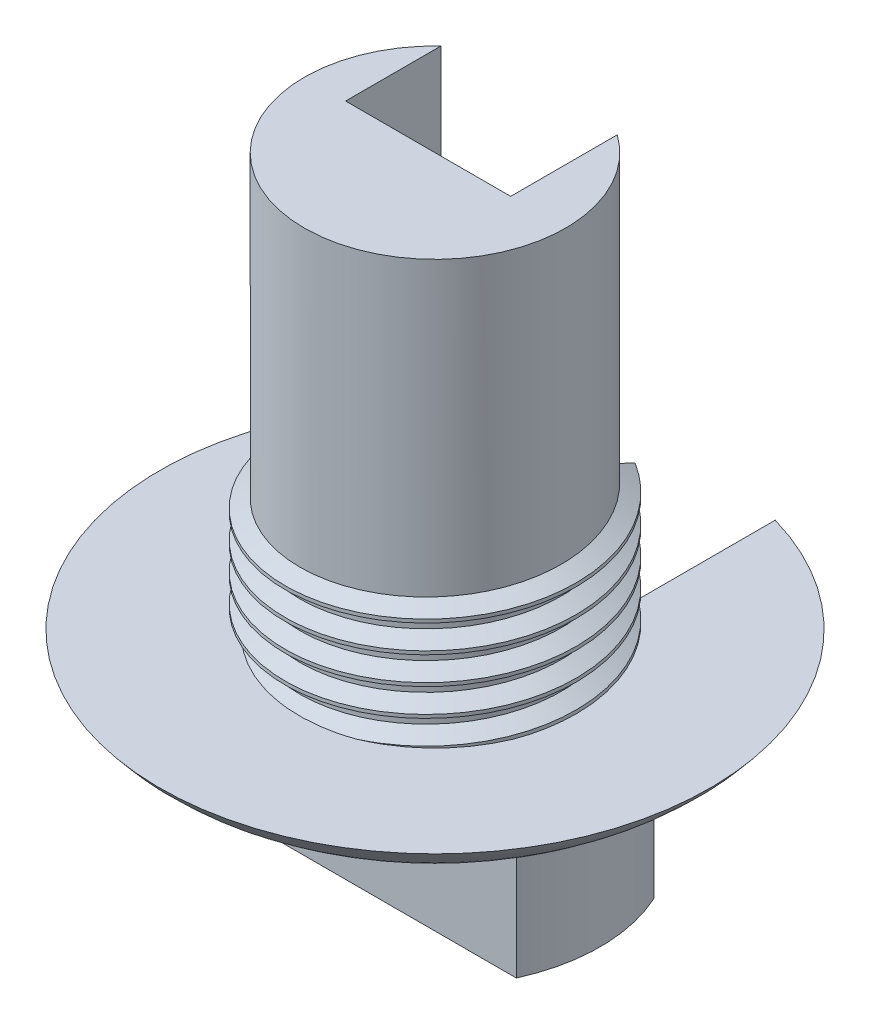
SolidWorks part; units mm, degrees
ref_plane "Alzado" through (0, 0, 0) normal (0, 0, 1) x (1, 0, 0)
ref_plane "Planta" through (0, 0, 0) normal (0, 1, 0) x (1, 0, 0)
ref_plane "Vista lateral" through (0, 0, 0) normal (1, 0, 0) x (0, 0, -1)
sketch "Croquis1" plane through (0, 0, 0) normal (0, 1, 0) x (1, 0, 0)
  circle A0 centre (0, 0) radius 20
  dimension "D1" = 40
extrude "Saliente-Extruir1" add sketch "Croquis1" along normal blind 4
sketch "Croquis2" plane through (0, 4, 0) normal (0, 1, 0) x (1, 0, 0)
  circle A0 centre (0, 0) radius 9.5
  dimension "D1" = 19
extrude "Saliente-Extruir2" add sketch "Croquis2" along normal blind 10
thread "Rosca1" pitch 2 method extrude profile "Perfil de rosca1" start angle 0, offset 0, length 12, pitch 2, diameter 19
ref_plane "Plano1" through (-9.5, 14, 0) normal (0, 0, 1) x (-1, 0, 0)
sketch "Perfil de rosca1" plane through (-9.5, 14, 0) normal (0, 0, 1) x (-1, 0, 0)
  line L0 (0, 0) -> (0, 2) construction
  line L1 (0, 0) -> (1.0825, 0.625)
  line L2 (1.0825, 0.625) -> (1.0825, 0.875)
  line L3 (1.0825, 0.875) -> (0, 1.5)
  line L4 (1.0825, 0.75) -> (0, 0.75) construction
  line L11 (0, 0) -> (0, 1.5)
  point P2 (0, 0)
  dimension "Pitch" = 2
  dimension "Profile_Angle" = 60
  dimension "Profile_Land" = 0.25
  dimension "Profile_Height" = 1.0825
fillet "Redondeo1" radius 10 1 edges at (0, 0, 20)
sketch "Croquis6" plane through (0, 0, 0) normal (0, 1, 0) x (1, 0, 0)
  line L1 (-10.9087, -5) -> (10.9087, -5)
  line L3 (-10.9087, 5) -> (10.9087, 5)
  circle A0 centre (0, 0) radius 12 construction
  arc A1 (10.9087, -5) -> (10.9087, 5) centre (0, 0) ccw
  arc A2 (-10.9087, 5) -> (-10.9087, -5) centre (0, 0) ccw
  dimension "D1" = 10
  dimension "D2" = 10
extrude "Saliente-Extruir3" add sketch "Croquis6" against normal blind 10 contours L3 A1 L1 A2
sketch "Croquis8" plane through (0, 14, 0) normal (0, 1, 0) x (1, 0, 0)
  circle A1 centre (0, 0) radius 9.5
  circle A2 centre (0, 0) radius 9.5
  dimension "D1" = 0
extrude "Saliente-Extruir4" add sketch "Croquis8" along normal blind 20
sketch "Croquis9" plane through (0, 0, 0) normal (0, 1, 0) x (1, 0, 0)
  line L0 (-6.5, 0) -> (5.5, 0)
  line L3 (-6.5, 0) -> (-6.5, 26.0113)
  line L4 (-6.5, 26.0113) -> (5.5, 26.0113)
  line L5 (5.5, 0) -> (5.5, 26.0113)
  dimension "D1" = 26.0113
  dimension "D2" = 12
  dimension "D3" = 5.5
extrude "Cortar-Extruir1" cut sketch "Croquis9" along normal blind 36 and the other way blind 36
